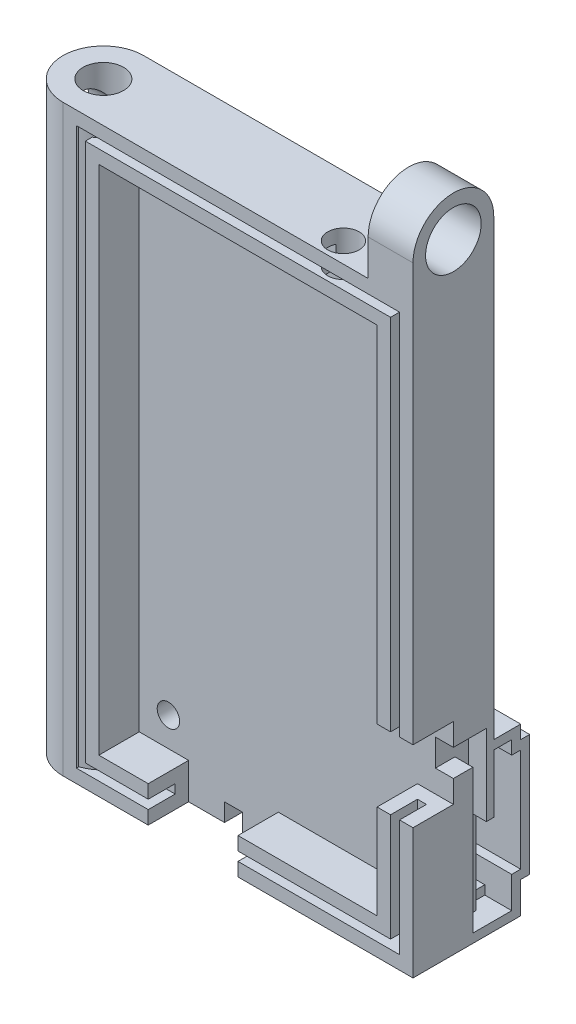
SolidWorks part; units mm, degrees
ref_plane "Front Plane" through (0, 0, 0) normal (0, 0, 1) x (1, 0, 0)
ref_plane "Top Plane" through (0, 0, 0) normal (0, 1, 0) x (1, 0, 0)
ref_plane "Right Plane" through (0, 0, 0) normal (1, 0, 0) x (0, 0, -1)
sketch "Sketch1" plane through (0, 0, 0) normal (0, 0, 1) x (1, 0, 0)
  line L1 (0, 0) -> (39, 0)
  line L2 (0, 0) -> (0, 65)
  line L3 (0, 65) -> (39, 65)
  line L4 (39, 0) -> (39, 65)
  dimension "D1" = 65
  dimension "D2" = 39
extrude "Base" add sketch "Sketch1" along normal blind 4.5
sketch "Sketch2" plane through (0, 0, 4.5) normal (0, 0, 1) x (1, 0, 0)
  line L0 (0, 65) -> (0, 0) construction
  line L1 (39, 65) -> (0, 65)
  line L2 (39, 65) -> (39, 61)
  line L3 (39, 61) -> (0, 61)
  line L4 (0, 65) -> (0, 61)
  line L5 (0, 0) -> (39, 0) construction
  line L6 (0, 61) -> (4, 61)
  line L7 (0, 61) -> (0, 0)
  line L8 (0, 0) -> (4, 0)
  line L9 (4, 61) -> (4, 0)
  line L10 (39, 0) -> (39, 65) construction
  line L11 (4, 0) -> (39, 0)
  line L12 (4, 0) -> (4, 4)
  line L13 (4, 4) -> (39, 4)
  line L14 (39, 0) -> (39, 4)
  line L16 (39, 61) -> (35, 61)
  line L17 (39, 61) -> (39, 4)
  line L18 (39, 4) -> (35, 4)
  line L19 (35, 61) -> (35, 4)
  line M6 (0, 65) -> (0, 0)
  line M7 (0, 0) -> (39, 0)
  line M8 (39, 0) -> (39, 65)
  line M9 (39, 65) -> (0, 65)
  dimension "D1" = 4
  dimension "D2" = 4
  dimension "D3" = 4
  dimension "D4" = 4
extrude "Walls" add sketch "Sketch2" along normal blind 4.5 contours L3 M8 M9 M6 | L3 L19 L13 M8 | L9 L3 M6 M7 | L13 L9 M7 M8 region at (19.5, 63, 4.5) region at (37, 32.5, 4.5) region at (2, 30.5, 4.5) region at (21.5, 2, 4.5)
sketch "Sketch3" plane through (0, 4, 0) normal (0, 1, 0) x (1, 0, 0)
  line L0 (4, -4.5) -> (35, -4.5) construction
  line L1 (9.5, -4.5) -> (19.5, -4.5)
  line L2 (9.5, -4.5) -> (9.5, -9)
  line L3 (9.5, -9) -> (19.5, -9)
  line L4 (19.5, -4.5) -> (19.5, -9)
  line L5 (4, -9) -> (35, -9) construction
  line L6 (4, -9) -> (4, -4.5) construction
  dimension "D1" = 5.5
  dimension "D2" = 15.5
extrude "PWR connector hole" cut sketch "Sketch3" against normal blind 4
sketch "Sketch4" plane through (35, 0, 0) normal (-1, 0, 0) x (0, 0, 1)
  line L0 (4.5, 61) -> (4.5, 4) construction
  line L1 (4.5, 14.5) -> (9, 14.5)
  line L2 (4.5, 14.5) -> (4.5, 22.5)
  line L3 (4.5, 22.5) -> (9, 22.5)
  line L4 (9, 14.5) -> (9, 22.5)
  line L5 (9, 61) -> (9, 4) construction
  line L6 (9, 4) -> (4.5, 4) construction
  dimension "D1" = 10.5
  dimension "D2" = 18.5
extrude "GPS connector hole" cut sketch "Sketch4" against normal blind 4
sketch "Sketch5" plane through (0, 0, 4.5) normal (0, 0, 1) x (1, 0, 0)
  line L0 (4, 4) -> (9.5, 4) construction
  line L1 (4, 61) -> (4, 4) construction
  line L2 (19.5, 61) -> (19.5, 4) construction
  line L3 (35, 61) -> (4, 61) construction
  line L5 (19.5, 32.5) -> (4, 32.5) construction
  line L6 (4, 61) -> (4, 4) construction
  circle A0 centre (7.25, 7.25) radius 1.25
  circle A1 centre (31.75, 7.25) radius 1.25
  circle A2 centre (7.25, 57.75) radius 1.25
  circle A3 centre (31.75, 57.75) radius 1.25
  dimension "D1" = 3.25
  dimension "D3" = 2.5
  dimension "D2" = 3.25
extrude "Mounting holes" cut sketch "Sketch5" against normal blind 4
sketch "Sketch7" plane through (0, 0, 0) normal (0, 0, -1) x (-1, 0, 0)
  line L0 (-39, 0) -> (-39, 18.5) construction
  line L1 (-39, 0) -> (-39, 65) construction
  line L3 (-39, 1) -> (-8, 1)
  line L4 (-39, 1) -> (-39, 17.5)
  line L5 (-39, 17.5) -> (-8, 17.5)
  line L6 (-8, 1) -> (-8, 17.5)
  line L9 (0, 0) -> (-39, 0) construction
  line L10 (-39, 0) -> (-7, 0)
  line L11 (-7, 0) -> (-7, 18.5)
  line L12 (-7, 18.5) -> (-39, 18.5)
  line L13 (-39, 18.5) -> (-39, 17.5)
  line L14 (-39, 1) -> (-39, 0)
  line M8 (-39, 65) -> (-39, 0)
  line M9 (-39, 0) -> (0, 0)
  dimension "D1" = 18.5
  dimension "D2" = 1
  dimension "D3" = 16.5
  dimension "D4" = 31
  dimension "D5" = 32
  dimension "D6" = 18.5
extrude "GPS mount" add sketch "Sketch7" along normal blind 3 contours L11 L12 L5 L6 L3 M8 M9 region at (23.5, 0.6304, 0)
sketch "Sketch8" plane through (8, 0, 0) normal (1, 0, 0) x (0, 0, -1)
  line L0 (3, 17.5) -> (0, 17.5) construction
  line L1 (1, 17.5) -> (2, 17.5)
  line L2 (1, 17.5) -> (1, 16.5)
  line L3 (1, 16.5) -> (2, 16.5)
  line L4 (2, 17.5) -> (2, 16.5)
  line L5 (0, 1) -> (0, 17.5) construction
  line L6 (0, 9.25) -> (3, 9.25) construction
  line L7 (3, 1) -> (3, 17.5) construction
  line L8 (1, 2) -> (2, 2)
  line L9 (2, 1) -> (2, 2)
  line L10 (1, 1) -> (2, 1)
  line L11 (1, 1) -> (1, 2)
  dimension "D1" = 1
  dimension "D2" = 1
  dimension "D3" = 1
extrude "GPS rails" add sketch "Sketch8" along normal blind 28
sketch "Sketch9" plane through (8, 0, 0) normal (1, 0, 0) x (0, 0, -1)
  line L1 (3, 1) -> (2, 1)
  line L2 (3, 1) -> (3, 17.5)
  line L3 (3, 17.5) -> (2, 17.5)
  line L4 (2, 1) -> (2, 17.5)
extrude "GPS \"roof\"" add sketch "Sketch9" along normal blind 14
sketch "Sketch10" plane through (22, 0, 0) normal (1, 0, 0) x (0, 0, -1)
  line L0 (3, 1) -> (3, 17.5) construction
  line L1 (2, 17.5) -> (3, 17.5)
  line L2 (2, 17.5) -> (2, 16)
  line L3 (2, 16) -> (3, 16)
  line L4 (3, 17.5) -> (3, 16)
  line L6 (2, 1) -> (3, 1)
  line L7 (2, 1) -> (2, 4.5)
  line L8 (2, 4.5) -> (3, 4.5)
  line L9 (3, 1) -> (3, 4.5)
  dimension "D1" = 1.5
  dimension "D2" = 3.5
extrude "GPS \"roof" add sketch "Sketch10" along normal blind 17
sketch "Sketch18" plane through (0, 0, -3) normal (0, 0, -1) x (-1, 0, 0)
  line L0 (-22, 4.5) -> (-22, 16) construction
  line L1 (-39, 4.5) -> (-21, 4.5)
  line L2 (-39, 4.5) -> (-39, 3.5)
  line L3 (-39, 3.5) -> (-21, 3.5)
  line L4 (-21, 4.5) -> (-21, 3.5)
  dimension "D1" = 1
  dimension "D2" = 1
extrude "Chip roof1" add sketch "Sketch18" along normal blind 1
sketch "Sketch19" plane through (0, 4.5, 0) normal (0, 1, 0) x (1, 0, 0)
  line L0 (39, 4) -> (39, 2) construction
  line L1 (21, 4) -> (39, 4)
  line L2 (21, 4) -> (21, 3)
  line L3 (21, 3) -> (39, 3)
  line L4 (39, 4) -> (39, 3)
extrude "Chip roof2" add sketch "Sketch19" along normal blind 12.5
sketch "Sketch11" plane through (0, 0, 0) normal (0, 0, -1) x (-1, 0, 0)
  line L0 (0, 0) -> (-7, 0) construction
  line L1 (-4, 0) -> (-5, 0)
  line L2 (-4, 0) -> (-4, 21.5)
  line L3 (-4, 21.5) -> (-5, 21.5)
  line L4 (-5, 0) -> (-5, 21.5)
  line L5 (-7, 0) -> (-7, 18.5) construction
  line L7 (0, 65) -> (0, 0) construction
  line L8 (-5, 21.5) -> (-22, 21.5)
  line L9 (-5, 21.5) -> (-5, 20.5)
  line L10 (-5, 20.5) -> (-22, 20.5)
  line L11 (-22, 21.5) -> (-22, 20.5)
  line L12 (-7, 18.5) -> (-39, 18.5) construction
  line L13 (-28, 18.5) -> (-27, 18.5)
  line L14 (-28, 18.5) -> (-28, 21.5)
  line L15 (-28, 21.5) -> (-27, 21.5)
  line L16 (-27, 18.5) -> (-27, 21.5)
  line M5 (-7, 0) -> (0, 0)
  line M9 (-39, 18.5) -> (-7, 18.5)
  dimension "D1" = 1
  dimension "D2" = 2
  dimension "D3" = 21.5
  dimension "D4" = 1
  dimension "D5" = 22
  dimension "D6" = 5
  dimension "D7" = 1
  dimension "D8" = 3
extrude "PWR cable holder1" add sketch "Sketch11" along normal blind 3 contours L4 L2 L3 M5 | L8 L11 L10 L4 | L16 L15 L14 M9 region at (4.5, 10.75, 0) region at (13.5, 21, 0) region at (27.5, 20, 0)
sketch "Sketch12" plane through (0, 0, 0) normal (0, -1, 0) x (1, 0, 0)
  line L0 (19.5, 4.5) -> (9.5, 4.5) construction
  line L1 (5, 0) -> (15.5, 0)
  line L2 (5, 0) -> (5, 2)
  line L3 (5, 2) -> (15.5, 2)
  line L4 (15.5, 0) -> (15.5, 2)
  line L5 (9.5, 4.5) -> (9.5, 9) construction
  line L6 (13.5, 4.5) -> (15.5, 4.5)
  line L7 (13.5, 4.5) -> (13.5, 2)
  line L8 (13.5, 2) -> (15.5, 2)
  line L9 (15.5, 4.5) -> (15.5, 2)
  line L10 (19.5, 9) -> (19.5, 4.5) construction
  line M5 (19.5, 4.5) -> (9.5, 4.5)
  line M13 (5, 0) -> (7, 0)
  dimension "D1" = 2
  dimension "D2" = 4
  dimension "D3" = 4
  dimension "D4" = 0
extrude "PWR cable holder2" cut sketch "Sketch12" against normal blind 2 contours L1 L4 L3 L2 M13 | L9 L7 L3 M5 region at (10.25, 0, 1) region at (14.5, 0, 3.25)
sketch "Sketch13" plane through (39, 0, 0) normal (1, 0, 0) x (0, 0, -1)
  line L0 (-4.5, 22.5) -> (-4.5, 14.5) construction
  line L1 (-4.5, 20) -> (-2.3266, 20)
  line L2 (-4.5, 20) -> (-4.5, 17)
  line L3 (-4.5, 17) -> (-2.3266, 17)
  line L4 (-2.3266, 20) -> (-2.3266, 17)
  line L5 (-9, 22.5) -> (-4.5, 22.5) construction
  line L6 (-4.5, 14.5) -> (-9, 14.5) construction
  line L7 (-2.3266, 17) -> (-2.3266, 11)
  line L8 (0, 1) -> (-2.3266, 1)
  line L9 (0, 1) -> (0, 11)
  line L10 (0, 11) -> (-2.3266, 11)
  line L11 (-2.3266, 1) -> (-2.3266, 11)
  line L18 (-2.3266, 11) -> (-0.8266, 11)
  line L19 (-2.3266, 11) -> (-2.3266, 20)
  line L20 (-2.3266, 20) -> (-0.8266, 20)
  line L21 (-0.8266, 11) -> (-0.8266, 20)
  line M19 (-4.5, 22.5) -> (-4.5, 14.5)
  line M27 (0, 1) -> (0, 17.5)
  dimension "D1" = 2.5
  dimension "D2" = 2.5
  dimension "D3" = 10
  dimension "D4" = 1.5
  dimension "D5" = 2.3266
extrude "GPS cable holder" cut sketch "Sketch13" against normal blind 2 contours L4 L1 L3 M19 | L10 L21 L20 L4 L7 | L11 L8 L10 M27 region at (39, 18.5, 3.4133) region at (39, 15.5, 1.5766) region at (39, 6, 1.1633)
sketch "Sketch14" plane through (0, 0, 9) normal (0, 0, 1) x (1, 0, 0)
  line L1 (1.5, 1.5) -> (2.5, 1.5)
  line L2 (1.5, 1.5) -> (1.5, 63.5)
  line L3 (1.5, 63.5) -> (2.5, 63.5)
  line L4 (2.5, 1.5) -> (2.5, 63.5)
  line L5 (0, 65) -> (0, 0) construction
  line L6 (4, 61) -> (4, 4) construction
  line L7 (39, 65) -> (0, 65) construction
  line L8 (35, 61) -> (4, 61) construction
  line L9 (2.5, 63.5) -> (37.5, 63.5)
  line L10 (2.5, 63.5) -> (2.5, 62.5)
  line L11 (2.5, 62.5) -> (37.5, 62.5)
  line L12 (37.5, 63.5) -> (37.5, 62.5)
  line L13 (39, 22.5) -> (39, 65) construction
  line L14 (19.5, 65) -> (19.5, 0) construction
  line L15 (0, 32.5) -> (39, 32.5) construction
  line L16 (37.5, 63.5) -> (36.5, 63.5)
  line L17 (36.5, 1.5) -> (36.5, 63.5)
  line L18 (37.5, 1.5) -> (36.5, 1.5)
  line L19 (37.5, 1.5) -> (37.5, 63.5)
  line L20 (2.5, 2.5) -> (37.5, 2.5)
  line L21 (37.5, 1.5) -> (37.5, 2.5)
  line L22 (2.5, 1.5) -> (37.5, 1.5)
  line L23 (2.5, 1.5) -> (2.5, 2.5)
  line M15 (35, 22.5) -> (39, 22.5)
  line M20 (9.5, 0) -> (9.5, 4)
  dimension "D2" = 1.5
  dimension "D3" = 1.5
  dimension "D4" = 1.5
  dimension "D5" = 1.5
extrude "Lid mount" cut sketch "Sketch14" against normal blind 3 contours L1 L4 L3 L2 | L4 L22 L20 M20 | L22 L17 L20 M20 | L20 L17 L18 L19 | L17 L20 L19 M15 | L19 L11 L17 M15 | L11 L17 L9 L4 | L17 L11 L12 L9 region at (2, 32.5, 9) region at (6, 2, 9) region at (23, 2, 9) region at (19.5, 63, 9) region at (37, 2, 9) region at (37, 63, 9) region at (37, 42.5, 9) region at (37, 12.5, 9)
sketch "Sketch15" plane through (0, 0, 0) normal (0, -1, 0) x (1, 0, 0)
  line L0 (0, 9) -> (0, 0) construction
  circle A0 centre (0, 4.5) radius 4.5
extrude "Ballon mount" add sketch "Sketch15" against normal blind 65
sketch "Sketch16" plane through (0, 0, 0) normal (0, -1, 0) x (1, 0, 0)
  line L0 (0, 0) -> (0, 4.5) construction
  circle A0 centre (0, 4.5) radius 2.25
  dimension "D1" = 4.5
extrude "Balloon mount hole" cut sketch "Sketch16" against normal blind 65
sketch "Sketch17" plane through (0, 0, 9) normal (0, 0, 1) x (1, 0, 0)
  line L0 (35, 61) -> (4, 61) construction
  line L1 (4, 4) -> (6, 4)
  line L2 (4, 4) -> (4, 61)
  line L3 (4, 61) -> (6, 61)
  line L4 (6, 4) -> (6, 61)
  dimension "D1" = 2
extrude "Correction" cut sketch "Sketch17" against normal blind 4.5
ref_plane "Plane1" through (-4.5, 0, 0) normal (-1, 0, 0) x (0, 0, 1)
sketch "Sketch21" plane through (-4.5, 0, 0) normal (-1, 0, 0) x (0, 0, 1)
  line L0 (4.5, 0) -> (4.5, 4.5) construction
  line L1 (0, 0) -> (9, 0) construction
  line L2 (0, 32.5) -> (9, 32.5) construction
  line L3 (0, 65) -> (0, 0) construction
  line L4 (9, 65) -> (9, 0) construction
  circle A0 centre (4.5, 4.5) radius 2.25
  circle A1 centre (4.5, 60.5) radius 2.25
  dimension "D2" = 4.5
  dimension "D1" = 4.5
extrude "Safety mount" cut sketch "Sketch21" against normal blind 4.5
sketch "Sketch22" plane through (0, 65, 0) normal (0, 1, 0) x (1, 0, 0)
  line L0 (39, 0) -> (0, 0) construction
  line L1 (39, -9) -> (34, -9)
  line L2 (39, -9) -> (39, 0)
  line L3 (39, 0) -> (34, 0)
  line L4 (34, -9) -> (34, 0)
  dimension "D1" = 5
extrude "Antenna mount base" add sketch "Sketch22" along normal blind 4
sketch "Sketch23" plane through (39, 0, 0) normal (1, 0, 0) x (0, 0, -1)
  line L0 (-9, 69) -> (0, 69) construction
  circle A0 centre (-4.5, 69) radius 4.5
extrude "Antenna mounting" add sketch "Sketch23" against normal blind 5
sketch "Sketch24" plane through (39, 0, 0) normal (1, 0, 0) x (0, 0, -1)
  line L0 (-9, 69) -> (-4.5, 69) construction
  circle A0 centre (-4.5, 69) radius 3.1
  dimension "D1" = 6.2
extrude "Antenna mount hole" cut sketch "Sketch24" against normal blind 5
sketch "Sketch25" plane through (0, 65, 0) normal (0, 1, 0) x (1, 0, 0)
  line L0 (34, -4.5) -> (0, -4.5) construction
  line L1 (34, 0) -> (34, -9) construction
  line L2 (29, -4.5) -> (29, -9) construction
  line L3 (34, -9) -> (0, -9) construction
  circle A0 centre (29, -6.75) radius 1.75
  dimension "D2" = 3.5
  dimension "D1" = 5
extrude "Antenna cable hole" cut sketch "Sketch25" against normal blind 4
